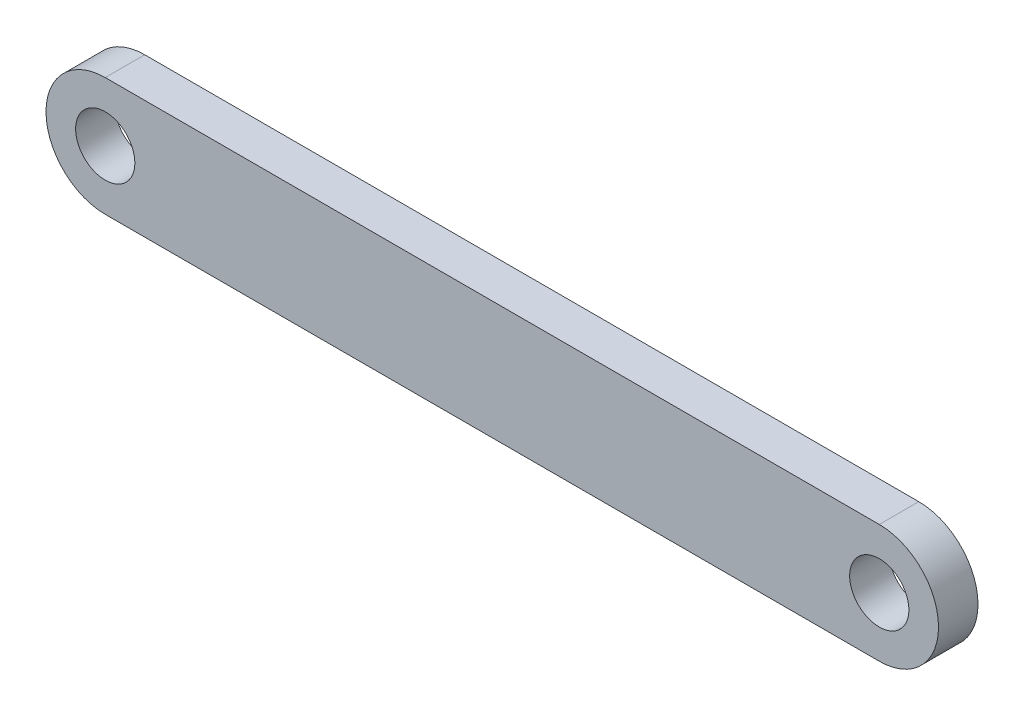
SolidWorks part; units mm, degrees
material "6061-T6 (SS)"
ref_plane "Front Plane" through (0, 0, 0) normal (0, 0, 1) x (1, 0, 0)
ref_plane "Top Plane" through (0, 0, 0) normal (0, 1, 0) x (1, 0, 0)
ref_plane "Right Plane" through (0, 0, 0) normal (1, 0, 0) x (0, 0, -1)
sketch "Sketch1" plane through (0, 0, 0) normal (0, 0, 1) x (1, 0, 0)
  line L1 (-62.6184, 19.05) -> (80.8916, 19.05)
  line L2 (-62.6184, 19.05) -> (-62.6184, 0)
  line L3 (-62.6184, 0) -> (80.8916, 0)
  line L4 (80.8916, 19.05) -> (80.8916, 0)
  dimension "D1" = 19.05
  dimension "D2" = 143.51
extrude "Boss-Extrude1" add sketch "Sketch1" along normal blind 6.35
sketch "Sketch3" plane through (0, 0, 0) normal (0, 0, 1) x (1, 0, 0)
  line L0 (-62.6184, 9.525) -> (80.8916, 9.525) construction
  line L1 (-62.6184, 19.05) -> (-62.6184, 0) construction
  line L2 (80.8916, 0) -> (80.8916, 19.05) construction
  circle A0 centre (-53.0934, 9.525) radius 4.7625
  circle A1 centre (71.3666, 9.525) radius 4.7625
  point P10 (9.1366, 9.525)
  point P11 (0, 0)
  point P12 (0, 0)
  dimension "D1" = 62.23
  dimension "D3" = 9.525
  dimension "D4" = 9.525
  dimension "D2" = 124.46
extrude "Cut-Extrude1" cut sketch "Sketch3" along normal blind 6.35
fillet "Fillet5" 2 edges at (-62.6184, 19.05, 3.175) (-62.6184, 0, 3.175) type full round first side face at (9.1366, 19.05, 3.175) second side face at (9.1366, 0, 3.175) middle face at (-62.6184, 9.525, 3.175)
fillet "Fillet6" 2 edges at (80.8916, 19.05, 3.175) (80.8916, 0, 3.175) type full round first side face at (13.8991, 19.05, 3.175) second side face at (13.8991, 0, 3.175) middle face at (80.8916, 9.525, 3.175)
equation "\"d\"= 0.375"
equation "\"l_long\"= 5.65"
equation "\"dist\"= 4.9"
equation "\"hdist\"= 2.45"
equation "\"thick\" = 0.25"
equation "\"height\" = 0.75"
equation "\"w\" = 8 / 2"
